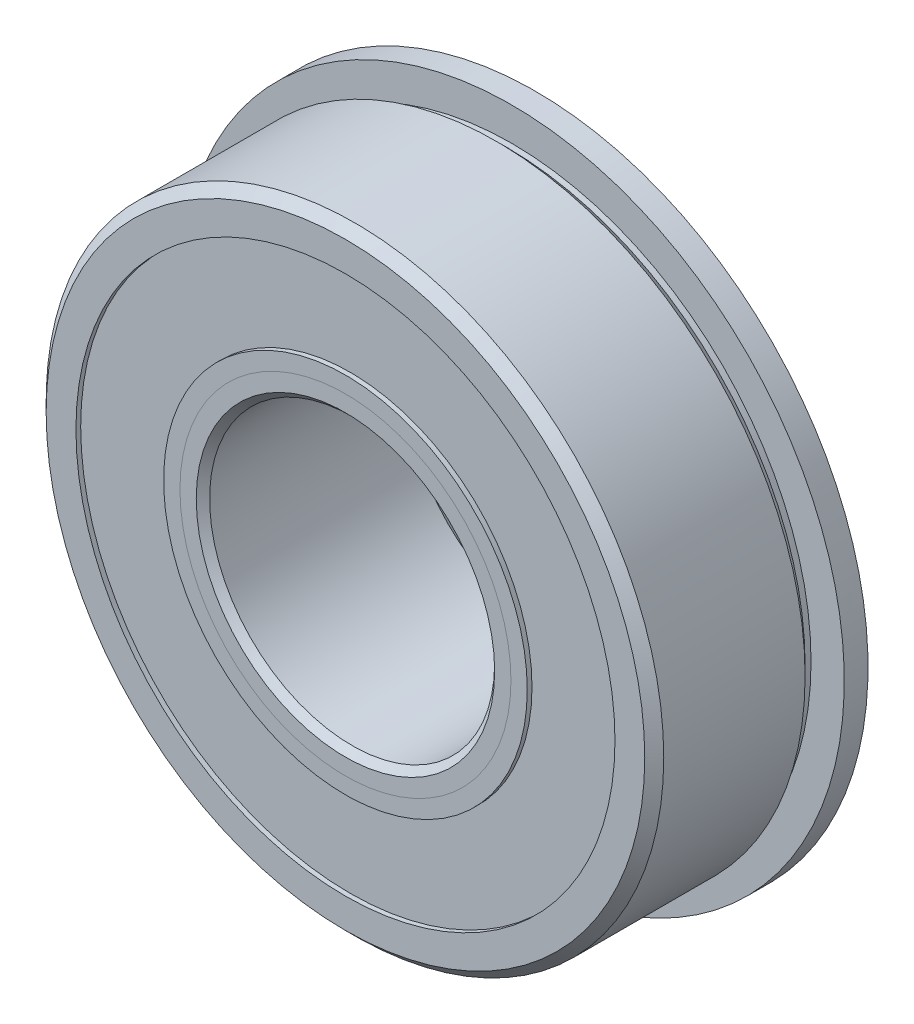
SolidWorks part; units mm, degrees
ref_plane "Front Plane" through (0, 0, 0) normal (0, 0, 1) x (1, 0, 0)
ref_plane "Top Plane" through (0, 0, 0) normal (0, 1, 0) x (1, 0, 0)
ref_plane "Right Plane" through (0, 0, 0) normal (1, 0, 0) x (0, 0, -1)
sketch "Sketch1" plane through (0, 0, 0) normal (1, 0, 0) x (0, 0, -1)
  line L0 (-6.35, 0) -> (6.35, 0) construction
  line L1 (0, 20.6375) -> (0, -20.6375) construction
  line L2 (5.715, 20.6375) -> (-5.715, 20.6375) construction
  line L3 (-5.715, 20.6375) -> (-6.35, 20.0025) construction
  line L4 (-6.35, 20.0025) -> (-6.35, 18.012) construction
  line L5 (-6.35, 18.012) -> (-3.6286, 18.012) construction
  line L6 (6.35, 18.012) -> (3.6286, 18.012) construction
  line L7 (6.35, 20.0025) -> (6.35, 18.012) construction
  line L8 (5.715, 20.6375) -> (6.35, 20.0025) construction
  line L9 (0, 20.6375) -> (0, 15.0813) construction
  line L10 (0, 15.0813) -> (0, 9.525) construction
  line L11 (6.35, 0) -> (7.9248, 0) construction
  line L12 (7.9248, 11.5062) -> (7.9248, -11.5062) construction
  line L13 (7.9248, -22.225) -> (7.9248, 22.225) construction
  arc A0 (-3.6286, 18.012) -> (3.6286, 18.012) centre (0, 15.0813) cw construction
  point P14 (0, 9.525)
  point P20 (7.9248, 0)
  point P23 (7.9248, 0)
  dimension "OD" = 41.275
  dimension "D1" = 45
  dimension "D2" = 0.635
  dimension "D3" = 7.2571
  dimension "D4" = 2.9308
  dimension "Width" = 12.7
  dimension "Total Wd" = 14.2748
  dimension "Shaft Dia" = 19.05
  dimension "Inner Ring OD" = 23.0124
  dimension "Flange OD" = 44.45
sketch "Sketch11" plane through (0, 0, 0) normal (0, 0, 1) x (1, 0, 0)
  circle A0 centre (0, 0) radius 9.525 construction
  dimension "Shaft Dia" = 19.05
sketch "Sketch8" plane through (0, 0, 0) normal (1, 0, 0) x (0, 0, -1)
  line L0 (5.715, 20.6375) -> (-5.715, 20.6375) construction
  line L1 (5.715, 20.6375) -> (6.35, 20.0025) construction
  line L2 (6.35, 20.0025) -> (6.35, 18.012) construction
  line L3 (6.35, 18.012) -> (3.6286, 18.012) construction
  line L4 (-6.35, 18.012) -> (-3.6286, 18.012) construction
  line L5 (-6.35, 20.0025) -> (-6.35, 18.012) construction
  line L6 (-5.715, 20.6375) -> (-6.35, 20.0025) construction
  line L7 (5.715, 20.6375) -> (-5.715, 20.6375)
  line L8 (5.715, 20.6375) -> (6.35, 20.0025)
  line L9 (6.35, 20.0025) -> (6.35, 18.012)
  line L10 (6.35, 18.012) -> (3.6286, 18.012)
  line L11 (-6.35, 18.012) -> (-3.6286, 18.012)
  line L12 (-6.35, 20.0025) -> (-6.35, 18.012)
  line L13 (-5.715, 20.6375) -> (-6.35, 20.0025)
  arc A0 (3.6286, 18.012) -> (-3.6286, 18.012) centre (0, 15.0813) ccw construction
  arc A1 (3.6286, 18.012) -> (-3.6286, 18.012) centre (0, 15.0813) ccw
revolve "Revolve7" add sketch "Sketch8" angle 360 about L0 region at (0, 20.2283, -5.9408)
sketch "Sketch2" plane through (0, 0, 0) normal (1, 0, 0) x (0, 0, -1)
  line L0 (-6.35, 12.1505) -> (-3.6286, 12.1505)
  line L2 (-6.35, 12.1505) -> (-6.35, 11.0607)
  line L3 (-6.35, 11.0607) -> (-5.2602, 9.971)
  line L4 (-5.2602, 9.971) -> (0, 9.971)
  line L5 (0, 20.6375) -> (0, -20.6375) construction
  line L6 (0, 9.971) -> (0, 10.4169)
  line L7 (0, 10.4169) -> (0, 9.525) construction
  line L8 (-6.35, 12.1505) -> (-6.35, 9.971) construction
  line L9 (-6.35, 9.971) -> (-5.2602, 9.971) construction
  line L10 (-6.35, 20.0025) -> (-6.35, -20.0025) construction
  arc A0 (-3.6286, 12.1505) -> (0, 10.4169) centre (0, 15.0813) ccw
  arc A1 (3.6286, 18.012) -> (-3.6286, 18.012) centre (0, 15.0813) ccw construction
  circle A2 centre (0, 15.0813) radius 4.6643 construction
  dimension "D1" = 45
revolve "Revolve2" add sketch "Sketch2" angle 360 about L0
sketch "Sketch3" plane through (0, 0, 0) normal (1, 0, 0) x (0, 0, -1)
  line L0 (-6.35, 11.0607) -> (-5.2602, 9.971)
  line L1 (-5.2602, 9.971) -> (0, 9.971)
  line L2 (0, 9.971) -> (0, 10.4169)
  line L3 (-6.35, 11.0607) -> (-6.35, 9.971)
  line L4 (-6.35, 12.1505) -> (-6.35, 9.971) construction
  line L5 (-6.35, 9.971) -> (-5.904, 9.525)
  line L6 (-5.904, 9.525) -> (7.2898, 9.525)
  line L7 (10.4392, 0) -> (-10.4392, 0) construction
  line L8 (7.2898, 9.525) -> (7.9248, 10.16)
  line L10 (7.9248, 10.16) -> (7.9248, 11.5062)
  line L11 (7.9248, 11.5062) -> (2.9958, 11.5062)
  line L13 (5.715, 20.6375) -> (6.35, 20.0025) construction
  circle A0 centre (0, 15.0813) radius 4.6643 construction
  arc A1 (2.9958, 11.5062) -> (0, 10.4169) centre (0, 15.0813) cw
  point P18 (0, 0)
  dimension "Inner Ring OD" = 23.0124
revolve "Revolve3" add sketch "Sketch3" angle 360 about L0
sketch "Sketch5" plane through (0, 0, 0) normal (1, 0, 0) x (0, 0, -1)
  line L0 (6.35, 20.0025) -> (6.35, 18.012) construction
  line L1 (6.35, 19.0073) -> (4.7625, 19.0073)
  line L2 (6.35, 19.0073) -> (6.35, 22.225)
  line L3 (6.35, 22.225) -> (4.7625, 22.225)
  line L4 (4.7625, 19.0073) -> (4.7625, 22.225)
  line L5 (7.9248, 0) -> (-6.35, 0) construction
  dimension "Flange OD" = 44.45
  dimension "D1" = 1.5875
revolve "Revolve5" add sketch "Sketch5" angle 360 about L5
sketch "Sketch6" plane through (0, 0, 0) normal (1, 0, 0) x (0, 0, -1)
  line L0 (3.7306, 20.6375) -> (4.3656, 20.0025)
  line L1 (5.715, 20.6375) -> (-5.715, 20.6375) construction
  line L2 (4.3656, 20.0025) -> (4.7625, 20.0025)
  line L3 (4.7625, 20.0025) -> (4.7625, 20.6375)
  line L4 (4.7625, 20.6375) -> (3.7306, 20.6375)
  line L5 (5.715, 20.6375) -> (6.35, 20.0025) construction
  line L6 (4.7625, 19.0073) -> (4.7625, 22.225) construction
  dimension "D1" = 0.3969
revolve "Cut-Revolve1" cut sketch "Sketch6" angle 360 about L0
sketch "Sketch4" plane through (0, 0, 0) normal (1, 0, 0) x (0, 0, -1)
  line L0 (-4.6643, 15.0813) -> (4.6643, 15.0813)
  circle A1 centre (0, 15.0813) radius 4.6643 construction
  arc A2 (-4.6643, 15.0813) -> (4.6643, 15.0813) centre (0, 15.0813) cw
  arc A3 (3.6286, 18.012) -> (-3.6286, 18.012) centre (0, 15.0813) ccw construction
revolve "Revolve4" add sketch "Sketch4" angle 360 about L0
ref_axis "Axis1" through (0, 0, -6.35) along (0, 0, 1)
pattern_circular "CirPattern1" count 14 over 360 about axis through (0, 0, 6.35) along (0, 0, -1) of bodies 104
sketch "Sketch7" plane through (0, 0, 0) normal (1, 0, 0) x (0, 0, -1)
  line L0 (-6.35, 18.012) -> (-3.6286, 18.012) construction
  line L1 (-6.0325, 18.012) -> (-4.6643, 18.012)
  line L2 (-6.0325, 18.012) -> (-6.0325, 12.1505)
  line L3 (-6.0325, 12.1505) -> (-4.6643, 12.1505)
  line L4 (-4.6643, 18.012) -> (-4.6643, 12.1505)
  line L5 (-6.35, 12.1505) -> (-3.6286, 12.1505) construction
  line L6 (-5.715, 20.6375) -> (-6.35, 20.0025) construction
  line L7 (6.35, 18.012) -> (3.6286, 18.012) construction
  line L8 (6.0325, 18.012) -> (4.6643, 18.012)
  line L9 (6.0325, 18.012) -> (6.0325, 11.5062)
  line L10 (6.0325, 11.5062) -> (4.6643, 11.5062)
  line L11 (4.6643, 18.012) -> (4.6643, 11.5062)
  line L12 (7.9248, 11.5062) -> (2.9958, 11.5062) construction
  line L13 (5.715, 20.6375) -> (6.35, 20.0025) construction
  circle A0 centre (0, 15.0813) radius 4.6643 construction
  point P10 (-6.0325, 20.32)
  point P21 (6.0325, 20.32)
revolve "Revolve6" add sketch "Sketch7" angle 360 about L0
sketch "Sketch9" plane through (0, 0, -7.9248) normal (0, 0, -1) x (-1, 0, 0)
  line L0 (0, 11.5062) -> (0, 10.16) construction
  circle A0 centre (0, 0) radius 10.16 construction
  circle A1 centre (0, 0) radius 11.5062
  circle A2 centre (0, 0) radius 11.5062 construction
  circle A3 centre (0, 0) radius 10.16 construction
  circle A4 centre (0, 0) radius 10.8331 construction
  circle A5 centre (0, 0) radius 11.0632
  circle A6 centre (0, 0) radius 10.603
  point P8 (0, 10.8331)
  dimension "D2" = 0.2301
  dimension "D3" = 0.2301
extrude "Cut-Extrude1" cut sketch "Sketch9" against normal blind 0.127
sketch "Sketch10" plane through (0, 0, -6.0325) normal (0, 0, -1) x (-1, 0, 0)
  circle A0 centre (0, 0) radius 11.5062 construction
  circle A1 centre (0, 0) radius 11.5062
  circle A2 centre (0, 0) radius 12.4267
  dimension "D1" = 0.9205
extrude "Cut-Extrude2" cut sketch "Sketch10" against normal blind 0.254
equation "\"D2@Sketch1\" = \"Width@Sketch1\"*.05"
equation "\"D3@Sketch1\"=\"Width@Sketch1\"/1.75"
equation "\"D4@Sketch1\"=(((\"OD@Sketch1\"-\"Width@Sketch1\")/2)/3.25)/1.5"
equation "\"Inner Ring OD@Sketch3\"=\"Inner Ring OD@Sketch1\""
equation "\"Flange OD@Sketch5\"=\"Flange OD@Sketch1\""
equation "\"D1@Sketch10\"=\"Inner Ring OD@Sketch1\"*.04"
equation "\"D2@Sketch9\"=\"Inner Ring OD@Sketch1\"*.01"
equation "\"D3@Sketch9\"=\"Inner Ring OD@Sketch1\"*.01"
equation "\"Shaft Dia@Sketch1\"=\"Shaft Dia@Sketch11\""
